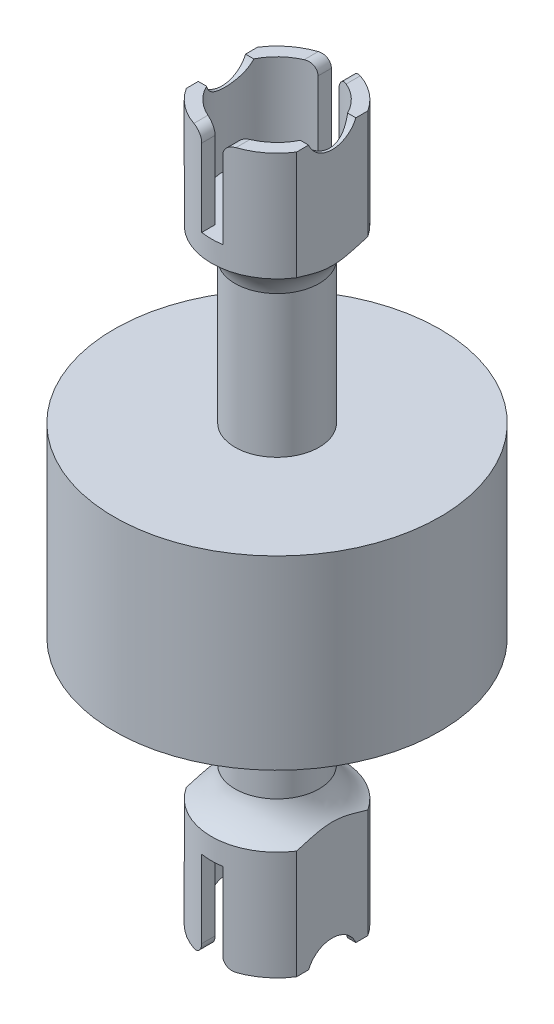
SolidWorks part; units mm, degrees
ref_plane "Front Plane" through (0, 0, 0) normal (0, 0, 1) x (1, 0, 0)
ref_plane "Top Plane" through (0, 0, 0) normal (0, 1, 0) x (1, 0, 0)
ref_plane "Right Plane" through (0, 0, 0) normal (1, 0, 0) x (0, 0, -1)
sketch "Sketch1" plane through (0, 0, 0) normal (0, 0, 1) x (1, 0, 0)
  line L0 (0, 0) -> (0, 68)
  line L1 (0, 32.5) -> (-15.5, 32.5) construction
  line L2 (-4, 54.8333) -> (-4, 41.3333)
  line L3 (0, 41.3333) -> (-15.5, 41.3333)
  line L4 (0, 23.6667) -> (-15.5, 23.6667)
  line L5 (-4, 13.1667) -> (-4, 23.6667)
  line L7 (-15.5, 41.3333) -> (-15.5, 23.6667)
  line L16 (-15.5, 34) -> (0, 34) construction
  line L17 (-6.25, 57.6333) -> (-6.25, 68)
  line L18 (-6.25, 68) -> (-2, 68)
  line L19 (-1, 67) -> (-1, 59.6333)
  line L20 (-1, 59.6333) -> (0, 59.6333)
  line L22 (-6.25, 10.3667) -> (-6.25, 0)
  line L23 (-1, 8.3667) -> (0, 8.3667)
  line L24 (-1, 1) -> (-1, 8.3667)
  line L25 (-6.25, 0) -> (-2, 0)
  arc A0 (-4, 54.8333) -> (-6.25, 57.6333) centre (-8.2732, 53.7036) ccw
  arc A1 (-2, 68) -> (-1, 67) centre (-2, 67) cw
  arc A2 (-4, 13.1667) -> (-6.25, 10.3667) centre (-8.2732, 14.2964) cw
  arc A3 (-2, 0) -> (-1, 1) centre (-2, 1) ccw
  point P19 (-15.5, 34)
  point P26 (0, 34)
  dimension "D14" = 1
  dimension "D8" = 18.3
  dimension "D9" = 4.42
  dimension "D1" = 68
  dimension "D2" = 15.5
  dimension "D3" = 4
  dimension "D4" = 8.8333
  dimension "D5" = 4
  dimension "D6" = 1.5
  dimension "D10" = 6.25
  dimension "D12" = 2.8
  dimension "D13" = 1
  dimension "D15" = 2
revolve "Revolve1" add sketch "Sketch1" angle 360 about L0
sketch "Sketch2" plane through (0, 0, 0) normal (0, 0, 1) x (1, 0, 0)
  line L0 (-1, 1) -> (-1, 8.3667) construction
  line L1 (0, 0) -> (0, 68) construction
  line L2 (-1, 59.6333) -> (0, 59.6333) construction
  line L3 (-1, 67) -> (-1, 59.6333) construction
  line L4 (-1, 1) -> (-1, 8.3667)
  line L5 (0, 0) -> (0, 68)
  line L6 (-1, 59.6333) -> (1, 59.6333)
  line L7 (-1, 67) -> (-1, 59.6333)
  line L8 (-1, 8.3667) -> (0, 8.3667) construction
  line L9 (-1, 8.3667) -> (1, 8.3667)
  line L10 (1, 67) -> (1, 59.6333)
  line L11 (1, 1) -> (1, 8.3667)
  line L12 (-2, 68) -> (2, 68)
  line L13 (-2, 0) -> (2, 0)
  arc A0 (-2, 0) -> (-1, 1) centre (-2, 1) ccw construction
  arc A1 (-1, 67) -> (-2, 68) centre (-2, 67) ccw construction
  arc A2 (-2, 0) -> (-1, 1) centre (-2, 1) ccw
  arc A3 (-1, 67) -> (-2, 68) centre (-2, 67) ccw
  arc A4 (1, 67) -> (2, 68) centre (2, 67) cw
  arc A5 (2, 0) -> (1, 1) centre (2, 1) cw
  point P0 (0, 8.3667)
extrude "Cut-Extrude1" cut sketch "Sketch2" against normal through all and the other way through all contours L13 A5 L11 L9 L5 | A2 L13 L5 L9 L4 | L7 L6 L10 A4 L12 A3 region at (-0.5181, 4.0843, 0) region at (0.5181, 4.0843, 0)
sketch "Sketch3" plane through (0, 68, 0) normal (0, 1, 0) x (1, 0, 0)
  circle A0 centre (0, 0) radius 5
  arc A1 (-2, 5.9214) -> (-2, -5.9214) centre (0, 0) ccw construction
  dimension "D1" = 1.25
extrude "Cut-Extrude2" cut sketch "Sketch3" against normal up to surface (8.3667 mm away)
sketch "Sketch4" plane through (0, 0, 0) normal (0, -1, 0) x (1, 0, 0)
  circle A0 centre (0, 0) radius 5
  circle A1 centre (0, 0) radius 6.25 construction
  dimension "D1" = 1.25
extrude "Cut-Extrude3" cut sketch "Sketch4" against normal up to surface (8.3667 mm away) up to face at (0, 8.3667, 0)
sketch3d "3DSketch1" plane through (0, 0, 0) normal (0, 0, 1) x (1, 0, 0)
sketch "Sketch5" plane through (-6.25, 0, 0) normal (-1, 0, 0) x (0, 0, 1)
  line L0 (5.9214, 68) -> (-5.9214, 68) construction
  line L1 (5.9214, 68) -> (-5.9214, 68)
  line L2 (0, 68) -> (0, 66.5) construction
  arc A0 (-2.25, 68) -> (2.25, 68) centre (0, 68.9375) ccw
  point P8 (0, 66.5)
  dimension "D1" = 4.5
  dimension "D2" = 1.5
extrude "Cut-Extrude4" cut sketch "Sketch5" against normal through all contours L2 L1 A0 | L1 L2 A0 region at (-6.25, 67.3807, 0.8937) region at (-6.25, 67.3807, -0.8937)
sketch "Sketch6" plane through (0, 0, 0) normal (0, 0, 1) x (1, 0, 0)
  line L0 (5.831, 68) -> (2, 68) construction
  line L1 (-2, 68) -> (-5.831, 68) construction
  line L2 (5.831, 68) -> (2, 68)
  line L3 (-2, 68) -> (-5.831, 68)
  line L4 (1, 59.6333) -> (-1, 59.6333) construction
  line L5 (1, 59.6333) -> (-1, 59.6333)
  line L6 (0, 59.6333) -> (0, 70.4858) construction
  line L7 (-5.25, 70.4858) -> (-5.25, 57.6333)
  line L8 (6.25, 57.6333) -> (-6.25, 57.6333) construction
  line L9 (6.25, 57.6333) -> (-6.25, 57.6333)
  line L10 (-5.25, 70.4858) -> (-7.2183, 70.4858)
  line L11 (-7.2183, 70.4858) -> (-7.2183, 57.6333)
  line L12 (-7.2183, 57.6333) -> (-6.25, 57.6333)
  line L13 (5.25, 70.4858) -> (5.25, 57.6333)
  line L14 (5.25, 70.4858) -> (7.2183, 70.4858)
  line L15 (7.2183, 70.4858) -> (7.2183, 57.6333)
  line L16 (7.2183, 57.6333) -> (6.25, 57.6333)
  line L17 (6.25, 10.3667) -> (-6.25, 10.3667) construction
  line L18 (6.25, 10.3667) -> (-5.25, 10.3667)
  line L19 (-1, 8.3667) -> (1, 8.3667) construction
  line L20 (-1, 8.3667) -> (1, 8.3667)
  line L21 (0, 8.3667) -> (0, -1.5567) construction
  line L22 (5.25, -1.5567) -> (5.25, 10.3667)
  line L23 (-5.25, -1.5567) -> (-5.25, 10.3667)
  line L24 (5.25, -1.5567) -> (7.2183, -1.5567)
  line L25 (7.2183, -1.5567) -> (7.2183, 10.3667)
  line L26 (7.2183, 10.3667) -> (6.25, 10.3667)
  line L27 (-5.25, -1.5567) -> (-7.2183, -1.5567)
  line L28 (-7.2183, 10.3667) -> (-7.2183, 13.1667)
  line L29 (-7.2183, -1.5567) -> (-7.2183, 10.3667)
  line L30 (-5.25, 10.3667) -> (-5.25, 13.1667)
  line L31 (-5.25, 13.1667) -> (-7.2183, 13.1667)
  line L32 (5.25, 10.3667) -> (5.25, 13.1667)
  line L33 (7.2183, 10.3667) -> (7.2183, 13.1667)
  line L34 (5.25, 13.1667) -> (7.2183, 13.1667)
  line L35 (-7.2183, 57.6333) -> (-7.2183, 54.8333)
  line L36 (-7.2183, 54.8333) -> (-5.25, 54.8333)
  line L37 (-5.25, 54.8333) -> (-5.25, 57.6333)
  line L38 (4, 54.8333) -> (-4, 54.8333) construction
  line L39 (4, 54.8333) -> (-4, 54.8333)
  line L40 (7.2183, 57.6333) -> (7.2183, 54.8333)
  line L41 (7.2183, 54.8333) -> (5.25, 54.8333)
  line L42 (5.25, 54.8333) -> (5.25, 57.6333)
  line L43 (4, 13.1667) -> (-4, 13.1667) construction
  line L44 (4, 13.1667) -> (-4, 13.1667)
  spline S0 degree 2 poles (6.25, 66.5) (5.9474, 67.276) (5.831, 68) knots 0 0 0 0.221734 0.221734 0.221734 weights 0.003813 0.004353 0.004893 construction
  spline S1 degree 2 poles (-5.831, 68) (-5.9474, 67.276) (-6.25, 66.5) knots 0.606349 0.606349 0.606349 1 1 1 weights 0.006768 0.007728 0.008687 construction
  spline S2 degree 2 poles (6.25, 66.5) (5.9474, 67.276) (5.831, 68) knots 0 0 0 0.221734 0.221734 0.221734 weights 0.003813 0.004353 0.004893
  spline S3 degree 2 poles (-5.831, 68) (-5.9474, 67.276) (-6.25, 66.5) knots 0.606349 0.606349 0.606349 1 1 1 weights 0.006768 0.007728 0.008687
  dimension "D1" = 5.25
  dimension "D2" = 5.25
  dimension "D3" = 1.9683
  dimension "D4" = 10.8524
  dimension "D5" = 9.9233
  dimension "D6" = 5.25
  dimension "D7" = 1.9683
extrude "Cut-Extrude6" cut sketch "Sketch6" against normal through all and the other way through all contours L11 L12 L9 L7 L10 | L16 L15 L14 L13 L9 | L29 L27 L23 L18 | L25 L26 L18 L22 L24 | L25 L24 L22 L32 L34 L33 | L35 L36 L37 L7 L10 L11 | L40 L41 L42 L13 L14 L15 region at (6.2342, 64.0596, 0) region at (-6.2342, 64.0596, 0) region at (6.2342, 4.405, 0) region at (-6.2342, 5.805, 0)
sketch "Sketch7" plane through (-6.25, 0, 0) normal (-1, 0, 0) x (0, 0, 1)
  line L0 (0, 0) -> (0, 1.5) construction
  line L1 (3.3912, 0) -> (-3.3912, 0) construction
  line L2 (-2.25, 0) -> (2.25, 0)
  arc A0 (-2.25, 0) -> (2.25, 0) centre (0, -0.9375) cw
  point P7 (0, 1.5)
  dimension "D1" = 1.5
  dimension "D2" = 4.5
extrude "Cut-Extrude9" cut sketch "Sketch7" against normal through all
sketch "Sketch8" plane through (0, 59.6333, 0) normal (0, 1, 0) x (1, 0, 0)
  circle A0 centre (0, 0) radius 2
  dimension "D1" = 4
extrude "Cut-Extrude10" cut sketch "Sketch8" against normal blind 3.5
sketch "Sketch10" plane through (0, 8.3667, 0) normal (0, -1, 0) x (1, 0, 0)
  circle A0 centre (0, 0) radius 2
  dimension "D1" = 4
extrude "Cut-Extrude11" cut sketch "Sketch10" against normal blind 3.5
